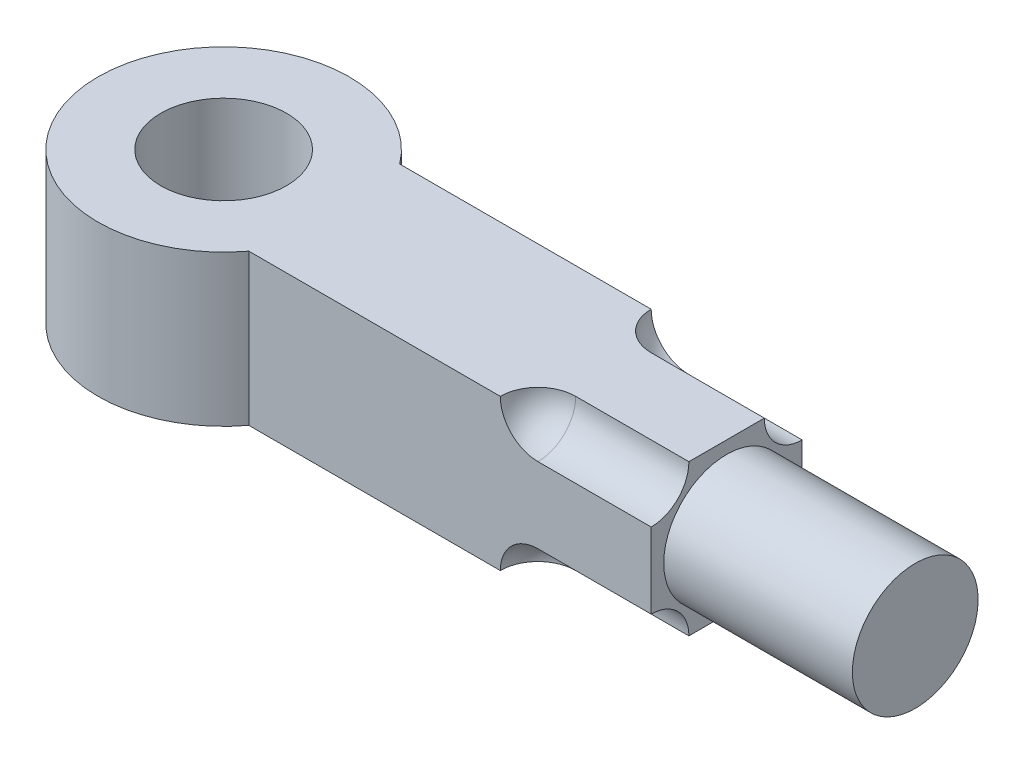
SolidWorks part; units mm, degrees
material "AISI 1020"
ref_plane "Front Plane" through (0, 0, 0) normal (0, 0, 1) x (1, 0, 0)
ref_plane "Top Plane" through (0, 0, 0) normal (0, 1, 0) x (1, 0, 0)
ref_plane "Right Plane" through (0, 0, 0) normal (1, 0, 0) x (0, 0, -1)
sketch "Sketch2" plane through (0, 0, 0) normal (0, 1, 0) x (1, 0, 0)
  line L1 (-24, 12) -> (40, 12)
  line L2 (-106.7068, 0) -> (106.7068, 0) construction
  line L4 (-24, -12) -> (40, -12)
  line L5 (40, 12) -> (40, -12)
  line L6 (0, -12) -> (0, 12) construction
  line L7 (-40, 0) -> (40, 0) construction
  arc A1 (-24, 12) -> (-24, -12) centre (-40, 0) ccw
  point P0 (0, 0)
  point P10 (0, 0)
  dimension "D1" = 24
  dimension "D3" = 40
extrude "Boss-Extrude1" add sketch "Sketch2" along normal blind 24 contours L4 L5 L1 A1
sketch "Sketch3" plane through (40, 0, 0) normal (1, 0, 0) x (0, 0, -1)
  circle A0 centre (0, 12) radius 10
  dimension "D1" = 20
extrude "Boss-Extrude2" add sketch "Sketch3" along normal blind 30
sketch "Sketch4" plane through (0, 24, 0) normal (0, 1, 0) x (1, 0, 0)
  circle A0 centre (-40, 0) radius 10
  dimension "D1" = 20
extrude "Cut-Extrude1" cut sketch "Sketch4" against normal through all both and the other way through all
sketch "Sketch7" plane through (40, 0, 0) normal (1, 0, 0) x (0, 0, -1)
  line L0 (-21.5806, 12) -> (21.5806, 12) construction
  line L1 (0, 27.7482) -> (0, -3.7482) construction
  line L2 (12, 0) -> (-12, 0) construction
  circle A0 centre (-12, 24) radius 6
  circle A1 centre (12, 24) radius 6
  circle A2 centre (12, 0) radius 6
  circle A3 centre (-12, 0) radius 6
  point P7 (0, 12)
  point P11 (0, 12)
  dimension "D1" = 12
  dimension "D2" = 12
extrude "Cut-Extrude2" cut sketch "Sketch7" against normal blind 24 and the other way through all
fillet "Fillet3" radius 6 4 edges at (16, 4.2426, -7.7574) (16, 4.2426, 7.7574) (16, 19.7574, -7.7574) (16, 19.7574, 7.7574)
